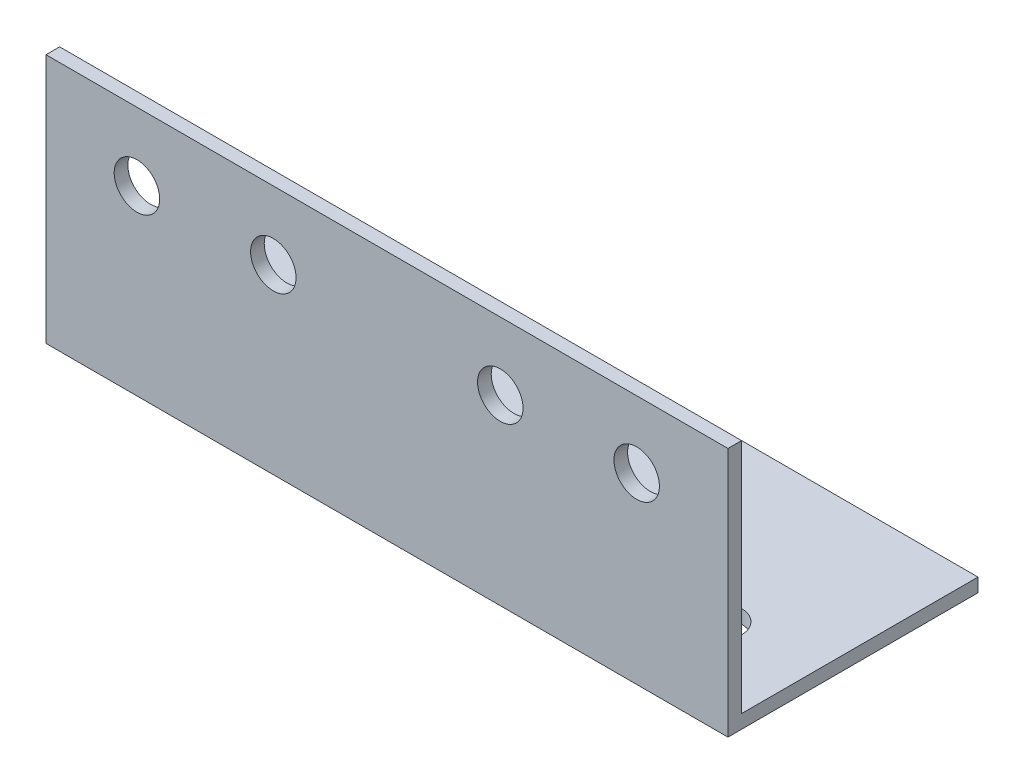
SolidWorks part; units mm, degrees
ref_plane "Спереди" through (0, 0, 0) normal (0, 0, 1) x (1, 0, 0)
ref_plane "Сверху" through (0, 0, 0) normal (0, 1, 0) x (1, 0, 0)
ref_plane "Справа" through (0, 0, 0) normal (1, 0, 0) x (0, 0, -1)
sketch "Эскиз1" plane through (0, 0, 0) normal (1, 0, 0) x (0, 0, -1)
  line L0 (0, 0) -> (0, 55)
  line L1 (0, 0) -> (55, 0)
extrude "Вытянуть-Тонкостенный1" add sketch "Эскиз1" along normal blind 150 thin thin type one direction reverse wall 3
sketch "Эскиз2" plane through (0, 0, 0) normal (0, 0, 1) x (1, 0, 0)
  line L0 (74.9233, 57.1633) -> (75, 25) construction
  circle A0 centre (20, 40) radius 5
  circle A1 centre (50, 40) radius 5
  circle A2 centre (99.9281, 40.1191) radius 5
  circle A3 centre (129.9278, 40.2622) radius 5
  dimension "D1" = 2
extrude "Вырез-Вытянуть1" cut sketch "Эскиз2" against normal through all
sketch "Эскиз3" plane through (0, 0, 0) normal (0, -1, 0) x (1, 0, 0)
  line L0 (75, -55.6806) -> (75, -1.3862) construction
  circle A0 centre (130, -18) radius 5
  circle A1 centre (100, -18) radius 5
  circle A2 centre (50, -18) radius 5
  circle A3 centre (20, -18) radius 5
  dimension "D1" = 2
extrude "Вырез-Вытянуть2" cut sketch "Эскиз3" against normal through all
